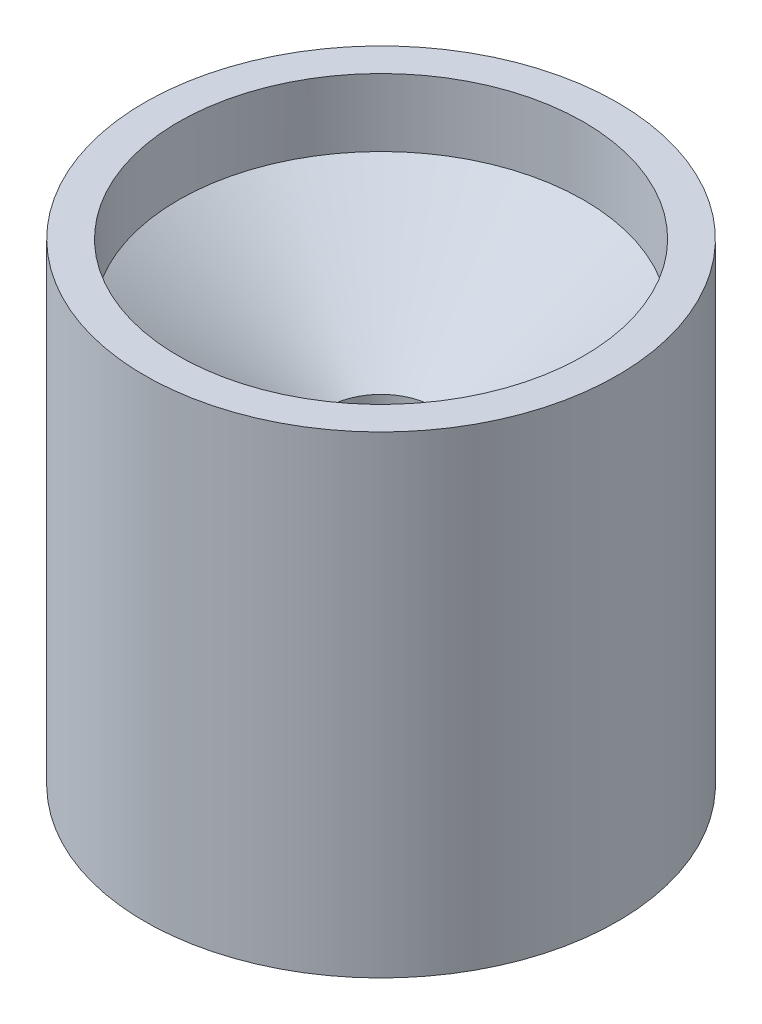
SolidWorks part; units mm, degrees
ref_plane "Front Plane" through (0, 0, 0) normal (0, 0, 1) x (1, 0, 0)
ref_plane "Top Plane" through (0, 0, 0) normal (0, 1, 0) x (1, 0, 0)
ref_plane "Right Plane" through (0, 0, 0) normal (1, 0, 0) x (0, 0, -1)
sketch "Sketch1" plane through (0, 0, 0) normal (0, 0, 1) x (1, 0, 0)
  line L0 (0, 0) -> (0, 76.2) construction
  line L1 (0, 0) -> (-44.45, 0) construction
  line L2 (-44.45, 0) -> (-44.45, 76.2)
  line L4 (-10.0076, 56.5295) -> (-10.0076, 50.1795)
  line L5 (-10.0076, 50.1795) -> (-23.4532, 0)
  line L6 (-23.4532, 0) -> (-44.45, 0)
  line L8 (-38.1, 76.2) -> (-10.0076, 56.5295)
  line L9 (-54.9705, 60.2512) -> (70.7588, 60.2512) construction
  line L11 (-44.45, 76.2) -> (-44.45, 88.9)
  line L12 (-44.45, 88.9) -> (-38.1, 88.9)
  line L13 (-38.1, 76.2) -> (-38.1, 88.9)
  dimension "D1" = 76.2
  dimension "D2" = 15
  dimension "D3" = 10.0076
  dimension "D4" = 12.7
  dimension "D5" = 44.45
  dimension "D6" = 6.35
  dimension "D7" = 6.35
  dimension "D8" = 20.9968
  dimension "D9" = 35
revolve "Revolve1" add sketch "Sketch1" angle 360 about L0
